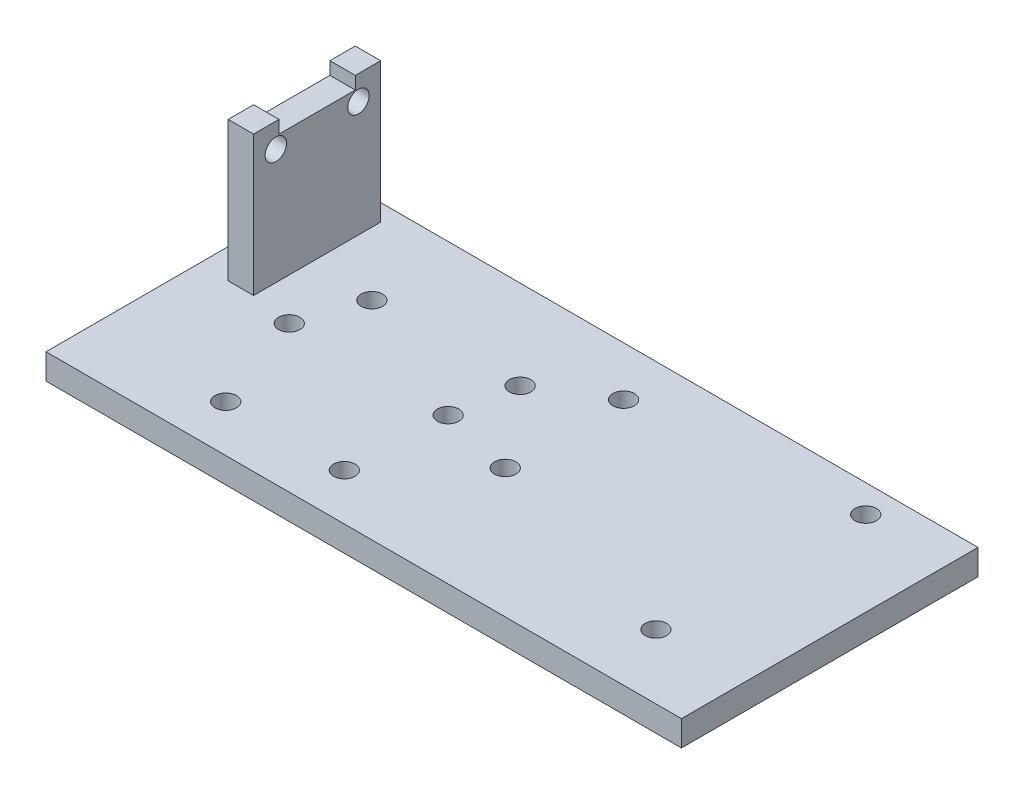
SolidWorks part; units mm, degrees
ref_plane "Front Plane" through (0, 0, 0) normal (0, 0, 1) x (1, 0, 0)
ref_plane "Top Plane" through (0, 0, 0) normal (0, 1, 0) x (1, 0, 0)
ref_plane "Right Plane" through (0, 0, 0) normal (1, 0, 0) x (0, 0, -1)
sketch "Sketch1" plane through (0, 0, 0) normal (0, 1, 0) x (1, 0, 0)
  line L1 (0, 0) -> (150, 0)
  line L2 (0, 0) -> (0, 70)
  line L3 (0, 70) -> (150, 70)
  line L4 (150, 0) -> (150, 70)
  dimension "D1" = 150
  dimension "D2" = 70
extrude "Boss-Extrude1" add sketch "Sketch1" along normal blind 6
hole_wizard "#8 (0.199) Diameter Hole1" positions "Sketch2" profile "Sketch3" hole size "#8" standard "ANSI Inch" end condition up to next
sketch "Sketch2" plane through (0, 6, 0) normal (0, 1, 0) x (1, 0, 0)
  point P0 (77.96, 58.38)
  point P3 (77.96, 30.44)
  point P6 (128.76, 15.2)
  point P9 (130.03, 63.46)
  point P12 (62.92, 49)
  point P15 (27.92, 49)
  point P18 (31.42, 11)
  point P21 (59.42, 11)
  point P24 (22.92, 34.5)
  point P27 (60.42, 34.5)
sketch "Sketch3" plane through (77.96, 6, -58.38) normal (1, 0, 0) x (0, 0, 1)
  line L0 (0, 0) -> (0, 6)
  line L1 (0, 6) -> (2.5273, 6)
  line L2 (2.5273, 6) -> (2.5273, 0)
  line L5 (2.5273, 0) -> (0, 0)
  line L11 (0, -6.35) -> (0, 107.95) construction
  dimension "Thru Hole Dia." = 5.0546
  dimension "Thru Hole Depth" = 6
sketch "Sketch4" plane through (0, 6, 0) normal (0, 1, 0) x (1, 0, 0)
  line L0 (150, 70) -> (0, 70) construction
  line L1 (7, 66) -> (13, 66)
  line L2 (7, 66) -> (7, 36)
  line L3 (7, 36) -> (13, 36)
  line L4 (13, 66) -> (13, 36)
  line L5 (0, 70) -> (0, 0) construction
  dimension "D1" = 30
  dimension "D2" = 6
  dimension "D3" = 4
  dimension "D4" = 7
extrude "Boss-Extrude2" add sketch "Sketch4" along normal blind 30
ref_plane "Plane1" through (0, 0, -51) normal (0, 0, -1) x (-1, 0, 0)
hole_wizard "#8 (0.199) Diameter Hole2" positions "Sketch5" profile "Sketch6" hole size "#8" standard "ANSI Inch" end condition up to next
sketch "Sketch5" plane through (7, 0, 0) normal (-1, 0, 0) x (0, 0, 1)
  point P0 (-41.25, 33.27)
  point P3 (-60.75, 33.27)
sketch "Sketch6" plane through (7, 33.27, -41.25) normal (0, 1, 0) x (0, 0, 1)
  line L0 (0, 0) -> (0, 6)
  line L1 (0, 6) -> (2.5273, 6)
  line L2 (2.5273, 6) -> (2.5273, 0)
  line L5 (2.5273, 0) -> (0, 0)
  line L11 (0, -6.35) -> (0, 107.95) construction
  dimension "Thru Hole Dia." = 5.0546
  dimension "Thru Hole Depth" = 6
sketch "Sketch7" plane through (0, 36, 0) normal (0, 1, 0) x (1, 0, 0)
  line L0 (13, 36) -> (13, 66) construction
  line L1 (7, 66) -> (13, 66)
  line L2 (7, 66) -> (7, 60)
  line L3 (7, 60) -> (13, 60)
  line L4 (13, 66) -> (13, 60)
  line L6 (7, 36) -> (13, 36)
  line L7 (7, 36) -> (7, 42)
  line L8 (7, 42) -> (13, 42)
  line L9 (13, 36) -> (13, 42)
  dimension "D1" = 6
  dimension "D2" = 6
extrude "Boss-Extrude3" add sketch "Sketch7" along normal blind 3
